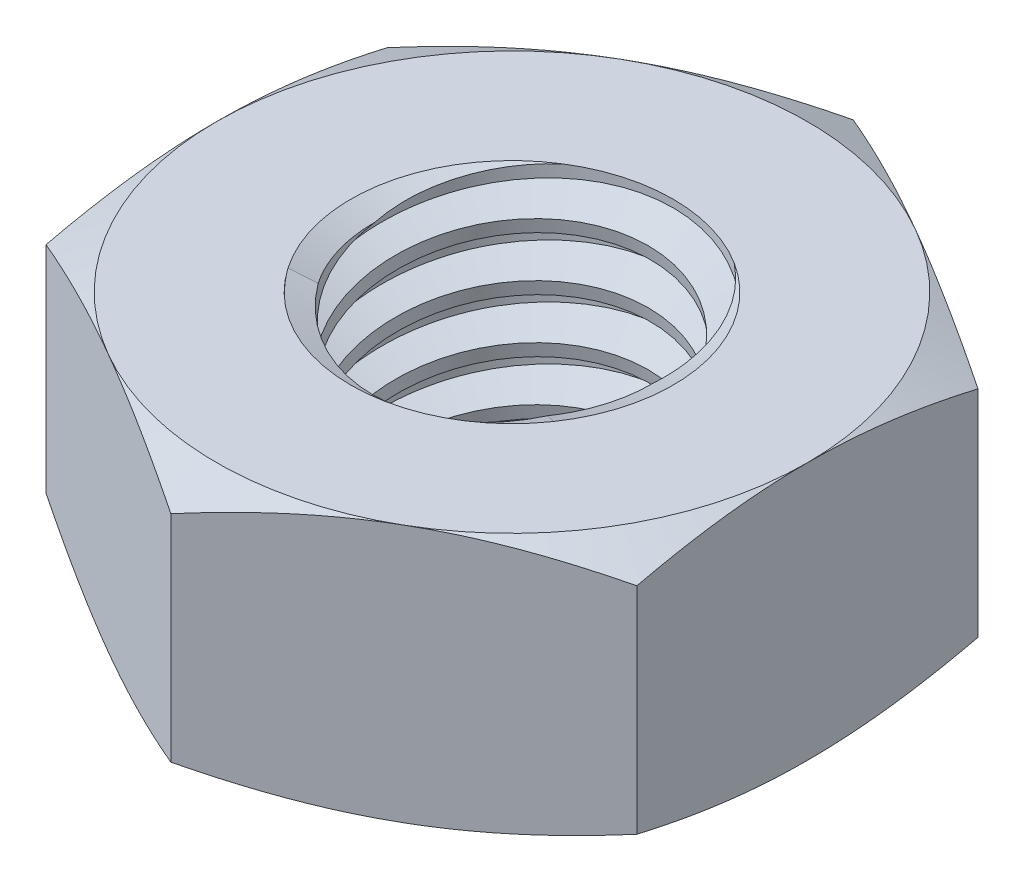
SolidWorks part; units mm, degrees
ref_plane "Front" through (0, 0, 0) normal (0, 0, 1) x (1, 0, 0)
ref_plane "Top" through (0, 0, 0) normal (0, 1, 0) x (1, 0, 0)
ref_plane "Right" through (0, 0, 0) normal (1, 0, 0) x (0, 0, -1)
sketch "Sketch1" plane through (0, 0, 0) normal (0, 1, 0) x (1, 0, 0)
  line L1 (0, 3.1754) -> (-2.75, 1.5877)
  line L2 (-2.75, 1.5877) -> (-2.75, -1.5877)
  line L3 (-2.75, -1.5877) -> (0, -3.1754)
  line L4 (0, -3.1754) -> (2.75, -1.5877)
  line L5 (2.75, -1.5877) -> (2.75, 1.5877)
  line L6 (2.75, 1.5877) -> (0, 3.1754)
  circle A0 centre (0, 0) radius 2.75 construction
  dimension "Hex Flats" = 5.5
extrude "Extrude1" add sketch "Sketch1" along normal mid plane 2.4
sketch "Sketch2" plane through (0, 0, 0) normal (1, 0, 0) x (0, 0, -1)
  line L0 (-1.5, -1.2) -> (-1.5, 1.2) construction
  line L1 (0, -1.2) -> (1.5, -1.2)
  line L2 (0, -1.2) -> (0, 1.2)
  line L3 (0, 1.2) -> (1.5, 1.2)
  line L4 (1.5, -1.2) -> (1.5, 1.2)
  line L5 (-1.5877, 1.2) -> (1.5877, 1.2) construction
  line L6 (-1.5877, -1.2) -> (1.5877, -1.2) construction
  line L7 (0, -2.7) -> (0, -1.2) construction
  dimension "Thread Dia" = 3
revolve "Revolve1" add sketch "Sketch2" angle 360 about L7
sketch "Sketch3" plane through (0, 0, 0) normal (1, 0, 0) x (0, 0, -1)
  line L0 (1.5, 1.2) -> (-1.5, 1.2) construction
  line L1 (-1.5, 1.2) -> (-1.5, 0.7) construction
  line L2 (-1.5, 0.7) -> (1.5, 1.2) construction
  line L3 (1.5, 1.2) -> (1.5103, 1.1384) construction
  line L4 (1.5103, 1.1384) -> (1.5822, 0.7068)
  line L5 (1.5822, 0.7068) -> (1.2896, 0.8164)
  line L6 (1.2896, 0.8164) -> (1.269, 0.9397)
  line L7 (1.269, 0.9397) -> (1.5103, 1.1384)
  line L8 (1.2793, 0.8781) -> (1.5462, 0.9226) construction
  line L9 (1.5, 1.2) -> (1.5, 0.9149) construction
  line L10 (1.5, 0.9149) -> (-1.5, 0.4149) construction
  line L11 (-1.5, 0.4149) -> (-1.5, 0.7) construction
  line L12 (-0.0892, 1.2) -> (0.0892, 0.1297) construction
  line L13 (-1.5, -1.2) -> (-1.5, 1.2) construction
  line L14 (0, 1.2) -> (1.5, 1.2) construction
  line L15 (1.5, -1.2) -> (1.5, 1.2) construction
  line L16 (0, 0) -> (0, 1.2) construction
  line L17 (-1.5103, 1.1384) -> (-1.5822, 0.7068) construction
  line L18 (-1.269, 0.9397) -> (-1.5103, 1.1384) construction
  line L19 (-1.2896, 0.8164) -> (-1.269, 0.9397) construction
  line L20 (-1.5822, 0.7068) -> (-1.2896, 0.8164) construction
  line L21 (0.0892, 1.2) -> (-0.0892, 0.1297) construction
  point P13 (0, 0.6649)
  dimension "D1" = 0.0625
  dimension "D2" = 0.125
  dimension "Thread Pitch" = 0.5
  dimension "D4" = 60
  dimension "D5" = 0.5
revolve "Cut-Revolve1" cut sketch "Sketch3" angle 360 about L12
pattern_linear "LPattern1" count 5 spacing 0.5 along (0, -1, 0) count 2 spacing 0.5 along (0, 1, 0) of "Cut-Revolve1"
sketch "Sketch4" plane through (0, 0, 0) normal (1, 0, 0) x (0, 0, -1)
  line L0 (0, 1.2) -> (1.5, 1.2)
  line L1 (1.5, 1.2) -> (1.269, 1.0923)
  line L2 (1.269, 1.0923) -> (1.269, -1.0923)
  line L3 (1.269, -1.0923) -> (1.5, -1.2)
  line L4 (1.5, -1.2) -> (0, -1.2)
  line L5 (0, -1.2) -> (0, 1.2)
  line L6 (1.5, -1.2) -> (1.5, 1.2) construction
  line L7 (0, 1.2) -> (1.5, 1.2) construction
  line L8 (0, -1.2) -> (1.5, -1.2) construction
  line L9 (0, -1.2) -> (0, 1.2) construction
  line L10 (0, 1.2) -> (0, 1.4549) construction
  dimension "D1" = 25
revolve "Cut-Revolve2" cut sketch "Sketch4" angle 360 about L10
combine bodies "Combine1" operation type subtract main body 112 bodies to subtract 111
sketch "Sketch5" plane through (0, 0, 0) normal (1, 0, 0) x (0, 0, -1)
  line L0 (0, -1.2) -> (2.75, -1.2)
  line L1 (2.75, -1.2) -> (3.1754, -1.0016)
  line L2 (3.1754, -1.0016) -> (3.1754, 1.0016)
  line L3 (3.1754, 1.0016) -> (2.75, 1.2)
  line L4 (0, 1.2) -> (0, 2.47)
  line L5 (0, 2.47) -> (4.4454, 2.47)
  line L6 (4.4454, 2.47) -> (4.4454, -2.47)
  line L7 (4.4454, -2.47) -> (0, -2.47)
  line L8 (0, -2.47) -> (0, -1.2)
  line L9 (2.75, 1.2) -> (2.75, -1.2) construction
  line L11 (0, -1.2) -> (1.5, -1.2) construction
  line L12 (2.75, 1.2) -> (0, 1.2)
  line L13 (3.1754, 0) -> (4.4454, 0) construction
  line L14 (3.1754, 1.2) -> (3.1754, -1.2) construction
  line L15 (0, -1.2) -> (0, 1.2) construction
  line L17 (0, 0) -> (2.75, 0) construction
  line L22 (0, 1.2) -> (1.5, 1.2) construction
  dimension "D1" = 25
  dimension "D2" = 1.27
  dimension "D3" = 2.4
revolve "Cut-Revolve3" cut sketch "Sketch5" angle 360 about L15
equation "\"D1@Sketch3\"=\"Thread Pitch@Sketch3\"/8"
equation "\"D2@Sketch3\"=\"Thread Pitch@Sketch3\"/4"
equation "\"D5@Sketch3\"=\"Thread Pitch@Sketch3\""
equation "\"D4@LPattern1\"=\"Thread Pitch@Sketch3\""
equation "\"D3@LPattern1\"=\"Thread Pitch@Sketch3\""
equation "\"D1@LPattern1\"=\"Height@Extrude1\"/\"Thread Pitch@Sketch3\""
